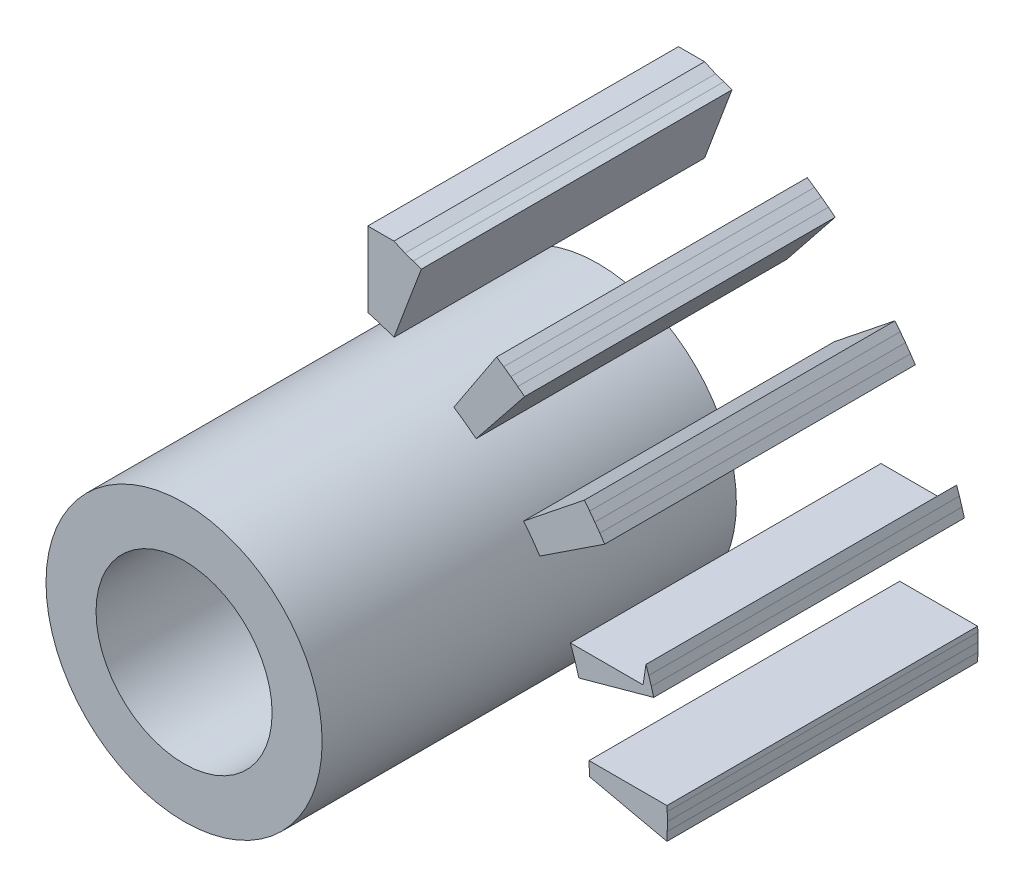
SolidWorks part; units mm, degrees
ref_plane "前视基准面" through (0, 0, 0) normal (0, 0, 1) x (1, 0, 0)
ref_plane "上视基准面" through (0, 0, 0) normal (0, 1, 0) x (1, 0, 0)
ref_plane "右视基准面" through (0, 0, 0) normal (1, 0, 0) x (0, 0, -1)
other "Configuration Table"
sketch "草图1" plane through (0, 0, 0) normal (0, 0, 1) x (1, 0, 0)
  circle A0 centre (0, 0) radius 8
  circle A1 centre (0, 0) radius 5.1
extrude "凸台-拉伸1" add sketch "草图1" along normal blind 24
extrude "凸台-拉伸2" add sketch "草图1<2>" along normal blind 24
sketch "草图1<2>" plane through (0, 0, 0) normal (0, 0, 1) x (1, 0, 0) same geometry as "草图1"
sketch "草图2" plane through (0, 0, 0) normal (0, 0, 1) x (1, 0, 0)
  line L0 (17.4637, 0.7961) -> (21.9772, 0.7961)
  line L1 (21.9772, 0.7961) -> (21.9943, 0.501)
  line L2 (21.9943, 0.501) -> (22, 0)
  line L3 (22, 0) -> (21.9943, -0.501)
  line L4 (21.9943, -0.501) -> (21.9772, -1.0018)
  line L5 (21.9772, -1.0018) -> (17.4818, 0)
  arc A0 (17.4818, 0) -> (17.4637, 0.7961) centre (0, 0) ccw
extrude "凸台-拉伸3" add sketch "草图2" along normal blind 18
sketch "草图3" plane through (0, 0, 0) normal (0, 0, 1) x (1, 0, 0)
  line L0 (16.38, 6.1601) -> (20.592, 6.1601)
  line L1 (20.592, 6.1601) -> (20.763, 7.2731)
  line L2 (20.763, 7.2731) -> (20.9232, 6.7984)
  line L3 (20.9232, 6.7984) -> (21.0726, 6.3201)
  line L4 (21.0726, 6.3201) -> (21.2111, 5.8385)
  line L5 (21.2111, 5.8385) -> (16.8725, 4.6443)
  arc A0 (16.8725, 4.6443) -> (16.38, 6.1601) centre (0, 0) ccw
extrude "凸台-拉伸4" add sketch "草图3" along normal blind 18
sketch "草图4" plane through (0, 0, 0) normal (0, 0, 1) x (1, 0, 0)
  line L0 (13.6747, 10.9203) -> (17.1911, 13.7284)
  line L1 (17.1911, 13.7284) -> (17.4993, 13.3333)
  line L2 (17.4993, 13.3333) -> (17.7984, 12.9313)
  line L3 (17.7984, 12.9313) -> (18.0883, 12.5226)
  line L4 (18.0883, 12.5226) -> (18.3688, 12.1074)
  line L5 (18.3688, 12.1074) -> (14.6115, 9.6309)
  arc A0 (14.6115, 9.6309) -> (13.6747, 10.9203) centre (0, 0) ccw
extrude "凸台-拉伸5" add sketch "草图4" along normal blind 18
sketch "草图5" plane through (0, 0, 0) normal (0, 0, 1) x (1, 0, 0)
  line L0 (9.6309, 14.6115) -> (12.1074, 18.3688)
  line L1 (12.1074, 18.3688) -> (12.5226, 18.0883)
  line L2 (12.5226, 18.0883) -> (12.9313, 17.7984)
  line L3 (12.9313, 17.7984) -> (13.3333, 17.4993)
  line L4 (13.3333, 17.4993) -> (13.7284, 17.1911)
  line L5 (13.7284, 17.1911) -> (10.9203, 13.6747)
  arc A0 (10.9203, 13.6747) -> (9.6309, 14.6115) centre (0, 0) ccw
extrude "凸台-拉伸6" add sketch "草图5" along normal blind 18
sketch "草图6" plane through (0, 0, 0) normal (0, 0, 1) x (1, 0, 0)
  line L0 (4.6443, 16.8725) -> (4.6443, 21.2111)
  line L1 (4.6443, 21.2111) -> (6.1601, 21.2111)
  line L2 (6.1601, 21.2111) -> (6.7984, 20.9232)
  line L3 (6.7984, 20.9232) -> (7.2731, 20.763)
  line L4 (7.2731, 20.763) -> (7.7441, 20.592)
  line L5 (7.7441, 20.592) -> (6.1601, 16.38)
  arc A0 (6.1601, 16.38) -> (4.6443, 16.8725) centre (0, 0) ccw
extrude "凸台-拉伸7" add sketch "草图6" along normal blind 18
